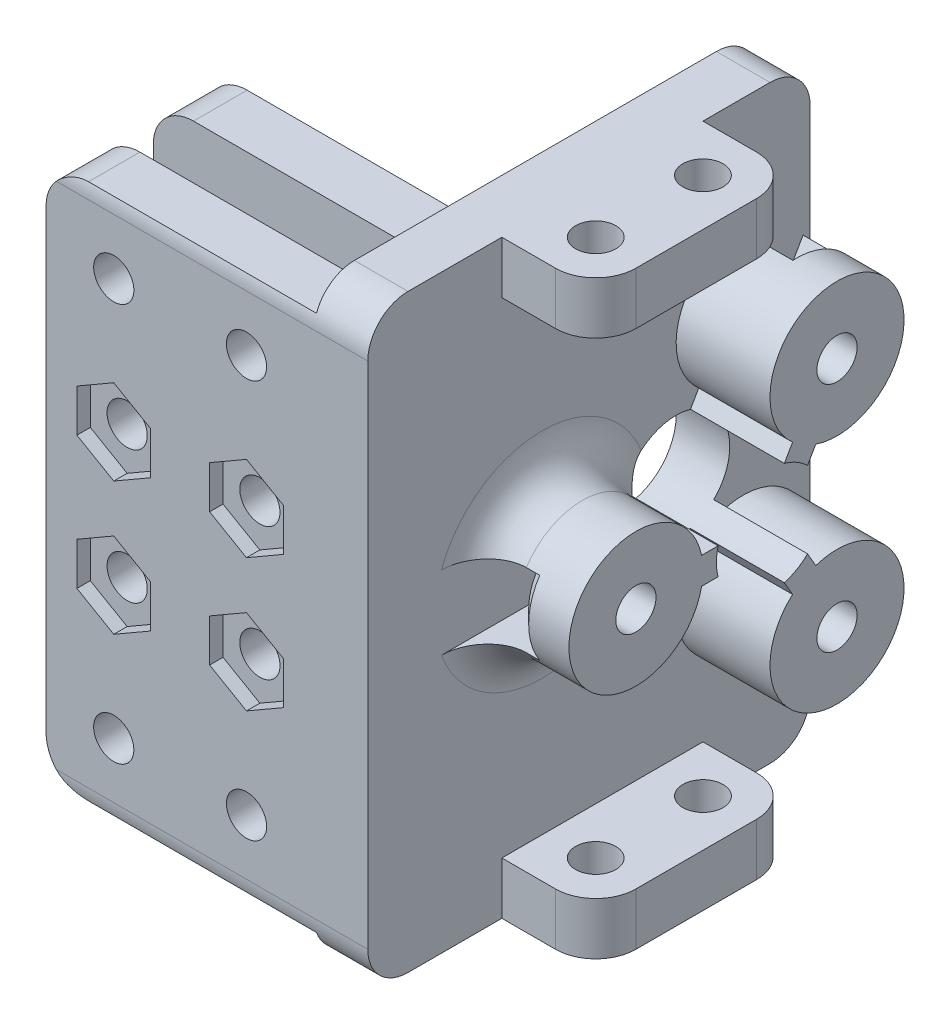
SolidWorks part; units mm, degrees
ref_plane "Спереди" through (0, 0, 0) normal (0, 0, 1) x (1, 0, 0)
ref_plane "Сверху" through (0, 0, 0) normal (0, 1, 0) x (1, 0, 0)
ref_plane "Справа" through (0, 0, 0) normal (1, 0, 0) x (0, 0, -1)
sketch "Sketch1" plane through (0, 0, 0) normal (0, 1, 0) x (1, 0, 0)
  line L5 (-12, -10) -> (12, -10)
  line L6 (-12, -10) -> (-12, 10)
  line L7 (-12, 10) -> (12, 10)
  line L8 (12, -10) -> (12, 10)
  line L9 (-12, -10) -> (12, 10) construction
  line L10 (-12, 10) -> (12, -10) construction
  point P0 (0, 0)
  dimension "D1" = 20
  dimension "D2" = 24
extrude "Boss-Extrude1" add sketch "Sketch1" along normal blind 52.2 contours L5 | L5 region at (0, 0, 0)
sketch "Sketch3" plane through (0, 0, 10) normal (0, 0, 1) x (1, 0, 0)
  line L0 (-12, 52.2) -> (-12, 0) construction
  line L1 (-12, 4) -> (8, 4)
  line L2 (-12, 4) -> (-12, 48.2)
  line L3 (-12, 48.2) -> (8, 48.2)
  line L4 (8, 4) -> (8, 48.2)
  line L5 (-12, 0) -> (12, 0) construction
  line L6 (12, 52.2) -> (12, 0) construction
  line L7 (-12, 52.2) -> (12, 52.2) construction
  dimension "D1" = 4
  dimension "D2" = 4
  dimension "D3" = 4
extrude "Cut-Extrude2" cut sketch "Sketch3" against normal blind 52.2
sketch "Sketch8" plane through (0, 0, 10) normal (0, 0, 1) x (1, 0, 0)
  line L8 (8, 4) -> (-12, 4)
  line L9 (-12, 4) -> (-12, 0)
  line L10 (-12, 0) -> (12, 0)
  line L11 (12, 0) -> (12, 52.2)
  line L12 (12, 52.2) -> (-12, 52.2)
  line L13 (-12, 52.2) -> (-12, 48.2)
  line L14 (-12, 48.2) -> (8, 48.2)
  line L15 (8, 48.2) -> (8, 4)
  line L16 (8, 4) -> (-12, 4)
  line L18 (-12, 0) -> (12, 0)
  line L19 (12, 0) -> (12, 52.2)
  line L20 (12, 52.2) -> (-12, 52.2)
  line L21 (-12, 52.2) -> (-12, 48.2)
  line L22 (-12, 48.2) -> (8, 48.2)
  line L23 (8, 48.2) -> (8, 4)
  line L24 (-12, 4) -> (-12, 0)
  dimension "D1" = 0
extrude "Boss-Extrude3" add sketch "Sketch8" along normal blind 7
sketch "Sketch9" plane through (0, 0, 17) normal (0, 0, 1) x (1, 0, 0)
  line L0 (-12, 0) -> (12, 0) construction
  line L1 (12, 52.2) -> (8, 52.2)
  line L2 (12, 52.2) -> (12, 0)
  line L3 (12, 0) -> (8, 0)
  line L4 (8, 52.2) -> (8, 0)
  dimension "D1" = 4
extrude "Boss-Extrude4" add sketch "Sketch9" along normal blind 6
sketch "Sketch12" plane through (8, 0, 0) normal (-1, 0, 0) x (0, 0, 1)
  line L0 (23, 52.2) -> (23, 0) construction
  line L1 (27, 46.1) -> (19, 46.1)
  line L2 (27, 46.1) -> (27, 6.1)
  line L3 (27, 6.1) -> (19, 6.1)
  line L4 (19, 46.1) -> (19, 6.1)
  line L5 (27, 46.1) -> (19, 6.1) construction
  line L6 (27, 6.1) -> (19, 46.1) construction
  point P0 (23, 26.1)
  line M5 (23, 0) -> (23, 52.2)
  dimension "D1" = 40
  dimension "D2" = 8
extrude "Boss-Extrude5" add sketch "Sketch12" along normal blind 20 contours L1 L4 L3 M5 region at (8, 26.1, 21)
sketch "Sketch13" plane through (0, 0, 23) normal (0, 0, 1) x (1, 0, 0)
  line L0 (8, 46.1) -> (-12, 6.1) construction
  line L1 (2.7339, 26.1) -> (-2.0002, 26.0996) construction
  line L2 (-2.0002, 26.0996) -> (-2.0002, 35.2652) construction
  circle A0 centre (2.9498, 40.95) radius 1.5
  circle A1 centre (2.9523, 11.25) radius 1.5
  circle A2 centre (-6.9527, 11.25) radius 1.5
  circle A3 centre (-6.9502, 40.95) radius 1.5
  dimension "D1" = 3
  dimension "D2" = 9.9
  dimension "D3" = 29.7
extrude "Cut-Extrude6" cut sketch "Sketch13" against normal blind 20
chamfer "Chamfer3" distance 3 angle 45 6 edges at (-2, 0, 17) (-2, 52.2, 17) (10, 52.2, 23) (0, 52.2, -10) (10, 0, 23) (0, 0, -10)
sketch "Sketch14" plane through (12, 0, 0) normal (1, 0, 0) x (0, 0, -1)
  line L0 (0, 52.2) -> (0, 0) construction
  line L1 (-20, 52.2) -> (7, 52.2) construction
  line L2 (-20, 0) -> (7, 0) construction
  line L3 (10, 49.2) -> (10, 3) construction
  circle A1 centre (0, 26.1) radius 4
  circle A2 centre (0, 26.1) radius 8
  dimension "D1" = 10
  dimension "D2" = 8
  dimension "D3" = 4
extrude "Cut-Extrude7" cut sketch "Sketch14" against normal blind 10 contours L0 A1 | A1 L0 region at (12, 26.1, -1.6977) region at (12, 26.1, 1.6977)
sketch "Sketch16" plane through (12, 0, 0) normal (1, 0, 0) x (0, 0, -1)
  line L0 (0, 26.1) -> (-25.7538, 26.1) construction
  circle A0 centre (-10, 26.1) radius 5
  point P12 (0, 26.1)
  dimension "D1" = 10
  dimension "D2" = 10
extrude "Boss-Extrude6" add sketch "Sketch16" along normal blind 7
sketch "Sketch17" plane through (12, 0, 0) normal (1, 0, 0) x (0, 0, -1)
  line L0 (-11.5877, 28.85) -> (-21.3317, 28.85)
  line L1 (-6.8246, 26.1) -> (-8.4123, 28.85)
  line L2 (-8.4123, 28.85) -> (-11.5877, 28.85)
  line L3 (-11.5877, 28.85) -> (-13.1754, 26.1)
  line L4 (-13.1754, 26.1) -> (-11.5877, 23.35)
  line L5 (-11.5877, 23.35) -> (-8.4123, 23.35)
  line L6 (-8.4123, 23.35) -> (-6.8246, 26.1)
  line L7 (-21.3317, 28.85) -> (-21.3317, 23.35)
  line L8 (-21.3317, 23.35) -> (-11.5877, 23.35)
  circle A0 centre (-10, 26.1) radius 2.75 construction
  circle M1 centre (-10, 26.1) radius 5
  dimension "D1" = 5.5
extrude "Cut-Extrude8" cut sketch "Sketch17" along normal blind 3 contours L7 L8 L0 M1 | L5 L6 L1 L2 L3 L4 | L8 L4 L3 L0 M1 region at (12, 26.1, 13.5261) region at (12, 26.1, 10) region at (12, 26.1, 18.0289)
sketch "Sketch18" plane through (19, 0, 0) normal (1, 0, 0) x (0, 0, -1)
  circle A0 centre (-10, 26.1) radius 1.5
  dimension "D1" = 3
extrude "Cut-Extrude9" cut sketch "Sketch18" against normal blind 7
chamfer "Chamfer4" distance 1 angle 45 1 edges at (15, 26.1, 15)
sketch "Sketch19" plane through (12, 0, 0) normal (1, 0, 0) x (0, 0, -1)
  line L1 (-2, 27.1) -> (-6, 27.1)
  line L2 (-2, 27.1) -> (-2, 25.1)
  line L3 (-2, 25.1) -> (-6, 25.1)
  line L4 (-6, 27.1) -> (-6, 25.1)
  line L5 (-2, 27.1) -> (-6, 25.1) construction
  line L6 (-2, 25.1) -> (-6, 27.1) construction
  circle A0 centre (0, 26.1) radius 4 construction
  point P0 (-4, 26.1)
  arc M23 (-14.1758, 28.85) -> (-14.1758, 23.35) centre (-10, 26.1) cw
  circle M28 centre (0, 26.1) radius 4
  dimension "D1" = 2
  dimension "D2" = 4
extrude "Boss-Extrude7" add sketch "Sketch19" along normal blind 7 contours L3 L1 M28 M23 region at (12, 26.1, 4.4955)
pattern_circular "CirPattern1" count 3 over 360 about axis through (2, 26.1, 0) along (1, 0, 0) of "Boss-Extrude6", "Cut-Extrude8", "Cut-Extrude9", "Chamfer4", "Boss-Extrude7" reverse direction yes
sketch "Sketch21" plane through (12, 0, 0) normal (1, 0, 0) x (0, 0, -1)
  line L0 (-20, 0) -> (7, 0) construction
  line L1 (-13, 4) -> (2, 4)
  line L2 (-13, 4) -> (-13, 8)
  line L3 (-13, 8) -> (2, 8)
  line L4 (2, 4) -> (2, 8)
  line L5 (-13, 4) -> (2, 8) construction
  line L6 (-13, 8) -> (2, 4) construction
  line L7 (10, 17.4397) -> (10, 3) construction
  line L8 (0, 26.1) -> (-26.3475, 26.1) construction
  point P0 (-5.5, 6)
  dimension "D1" = 4
  dimension "D2" = 15
  dimension "D3" = 4
  dimension "D4" = 8
extrude "Boss-Extrude8" add sketch "Sketch21" along normal up to surface (7 mm away) up to face at (19, 18.7388, -4.25)
fillet "Fillet3" radius 3 2 edges at (19, 6, 13) (19, 6, -2)
sketch "Sketch22" plane through (0, 4, 0) normal (0, -1, 0) x (1, 0, 0)
  line L0 (19, 5.5) -> (13.2888, 5.5) construction
  line L1 (19, 10) -> (19, 1) construction
  line L2 (12, 20) -> (12, -7) construction
  circle A0 centre (15.5, 9.5) radius 1.5
  circle A2 centre (15.5, 1.5) radius 1.5
  dimension "D1" = 3
  dimension "D2" = 8
  dimension "D3" = 3.5
extrude "Cut-Extrude10" cut sketch "Sketch22" against normal blind 10
sketch "Sketch23" plane through (12, 0, 0) normal (1, 0, 0) x (0, 0, -1)
  line L0 (0, 26.1) -> (13.0368, 26.1) construction
ref_plane "Plane1" through (0, 26.1, 0) normal (0, 1, 0) x (1, 0, 0)
mirror "Mirror1" about plane through (0, 26.1, 0) normal (0, 1, 0) of "Boss-Extrude8", "Fillet3", "Cut-Extrude10"
fillet "Fillet4" radius 3 2 edges at (12, 21.1905, 9.0532) (12, 31.0095, 9.0532)
sketch "Sketch24" plane through (8, 0, 0) normal (-1, 0, 0) x (0, 0, 1)
  line L0 (19, 46.1) -> (19, 6.1) construction
  line L1 (15, 6.1) -> (11, 6.1)
  line L2 (15, 6.1) -> (15, 46.1)
  line L3 (15, 46.1) -> (11, 46.1)
  line L4 (11, 6.1) -> (11, 46.1)
  line L5 (15, 6.1) -> (11, 46.1) construction
  line L6 (15, 46.1) -> (11, 6.1) construction
  point P0 (13, 26.1)
  point P5 (0, 26.1)
  point P6 (0, 0)
  dimension "D1" = 40
  dimension "D2" = 4
  dimension "D3" = 4
extrude "Boss-Extrude9" add sketch "Sketch24" along normal up to surface (20 mm away) up to face at (-12, 26.1, 21)
sketch "Sketch25" plane through (0, 0, 11) normal (0, 0, -1) x (-1, 0, 0)
  line L0 (12, 26.1) -> (2, 26.1) construction
  line L1 (12, 46.1) -> (12, 6.1) construction
  line L2 (2, 26.1) -> (2, 35.1897) construction
  line L3 (-8, 48.2) -> (-8, 4) construction
  circle A0 centre (6.95, 31.05) radius 1.5
  circle A1 centre (6.95, 21.15) radius 1.5
  circle A2 centre (-2.95, 21.15) radius 1.5
  circle A3 centre (-2.95, 31.05) radius 1.5
  dimension "D1" = 3
  dimension "D2" = 9.9
  dimension "D3" = 9.9
extrude "Cut-Extrude11" cut sketch "Sketch25" against normal blind 45
chamfer "Chamfer5" distance 2 angle 45 4 edges at (-8.45, 31.05, 11) (4.45, 31.05, 11) (1.45, 21.15, 11) (-5.45, 21.15, 11)
sketch "Sketch26" plane through (0, 0, 23) normal (0, 0, 1) x (1, 0, 0)
  line L0 (2.95, 17.9746) -> (5.7, 19.5623)
  line L1 (-6.95, 17.9746) -> (-4.2, 19.5623)
  line L2 (-4.2, 19.5623) -> (-4.2, 22.7377)
  line L3 (-4.2, 22.7377) -> (-6.95, 24.3254)
  line L4 (-6.95, 24.3254) -> (-9.7, 22.7377)
  line L5 (-9.7, 22.7377) -> (-9.7, 19.5623)
  line L6 (-9.7, 19.5623) -> (-6.95, 17.9746)
  line L7 (5.7, 19.5623) -> (5.7, 22.7377)
  line L8 (5.7, 22.7377) -> (2.95, 24.3254)
  line L9 (2.95, 24.3254) -> (0.2, 22.7377)
  line L10 (0.2, 22.7377) -> (0.2, 19.5623)
  line L11 (0.2, 19.5623) -> (2.95, 17.9746)
  line L12 (2.95, 27.8746) -> (5.7, 29.4623)
  line L13 (5.7, 29.4623) -> (5.7, 32.6377)
  line L14 (5.7, 32.6377) -> (2.95, 34.2254)
  line L15 (2.95, 34.2254) -> (0.2, 32.6377)
  line L16 (0.2, 32.6377) -> (0.2, 29.4623)
  line L17 (0.2, 29.4623) -> (2.95, 27.8746)
  line L18 (-6.95, 27.8746) -> (-4.2, 29.4623)
  line L19 (-4.2, 29.4623) -> (-4.2, 32.6377)
  line L20 (-4.2, 32.6377) -> (-6.95, 34.2254)
  line L21 (-6.95, 34.2254) -> (-9.7, 32.6377)
  line L22 (-9.7, 32.6377) -> (-9.7, 29.4623)
  line L23 (-9.7, 29.4623) -> (-6.95, 27.8746)
  circle A0 centre (-6.95, 21.15) radius 2.75 construction
  dimension "D1" = 5.5
  dimension "D2" = 2
  dimension "D3" = 2
extrude "Cut-Extrude12" cut sketch "Sketch26" against normal blind 1
sketch "Sketch27" plane through (-12, 0, 0) normal (-1, 0, 0) x (0, 0, 1)
  line L0 (-7, 0) -> (14, 0) construction
  line L1 (14, 0) -> (17, 3) construction
  line L2 (17, 3) -> (17, 4) construction
  line L3 (17, 4) -> (-10, 4) construction
  line L4 (-10, 4) -> (-10, 3) construction
  line L5 (-10, 3) -> (-7, 0) construction
  line L6 (17, 48.2) -> (17, 49.2) construction
  line L7 (17, 49.2) -> (14, 52.2) construction
  line L8 (14, 52.2) -> (-7, 52.2) construction
  line L9 (-7, 52.2) -> (-10, 49.2) construction
  line L10 (-10, 49.2) -> (-10, 48.2) construction
  line L11 (-10, 48.2) -> (17, 48.2) construction
  line L12 (-7, 0) -> (14, 0)
  line L13 (14, 0) -> (17, 3)
  line L14 (17, 3) -> (17, 4)
  line L15 (17, 4) -> (-10, 4)
  line L16 (-10, 4) -> (-10, 3)
  line L17 (-10, 3) -> (-7, 0)
  line L18 (17, 48.2) -> (17, 49.2)
  line L19 (17, 49.2) -> (14, 52.2)
  line L20 (14, 52.2) -> (-7, 52.2)
  line L21 (-7, 52.2) -> (-10, 49.2)
  line L22 (-10, 49.2) -> (-10, 48.2)
  line L23 (-10, 48.2) -> (17, 48.2)
extrude "Cut-Extrude13" cut sketch "Sketch27" against normal blind 20
sketch "Sketch28" plane through (8, 0, 0) normal (-1, 0, 0) x (0, 0, 1)
  line L0 (23, 4.1) -> (-10, 4.1)
  line L1 (11, 6.1) -> (15, 6.1) construction
  line L2 (23, 6.1) -> (23, 3) construction
  line L3 (-10, 49.2) -> (-10, 3) construction
  line L4 (0, 26.1) -> (-15.8704, 26.1) construction
  line L5 (23, 48.1) -> (-10, 48.1)
  line M2 (23, 46.1) -> (23, 49.2)
  line M3 (23, 49.2) -> (20, 52.2)
  line M4 (20, 52.2) -> (-7, 52.2)
  line M5 (-7, 52.2) -> (-10, 49.2)
  line M6 (-10, 49.2) -> (-10, 3)
  line M7 (-10, 3) -> (-7, 0)
  line M8 (-7, 0) -> (20, 0)
  line M9 (20, 0) -> (23, 3)
  line M10 (23, 3) -> (23, 6.1)
  dimension "D1" = 2
extrude "Cut-Extrude14" cut sketch "Sketch28" against normal blind 20 contours L0 M10 M6 M7 M8 M9 | L5 M2 M3 M4 M5 M6 region at (8, 2.1248, 6.5) region at (8, 50.0752, 6.5)
fillet "Fillet5" radius 3 4 edges at (10, 4.1, -10) (10, 48.1, -10) (10, 4.1, 23) (10, 48.1, 23)
fillet "Fillet6" radius 3 4 edges at (-12, 6.1, 13) (-12, 6.1, 20.9142) (-12, 46.1, 20.9142) (-12, 46.1, 13)
